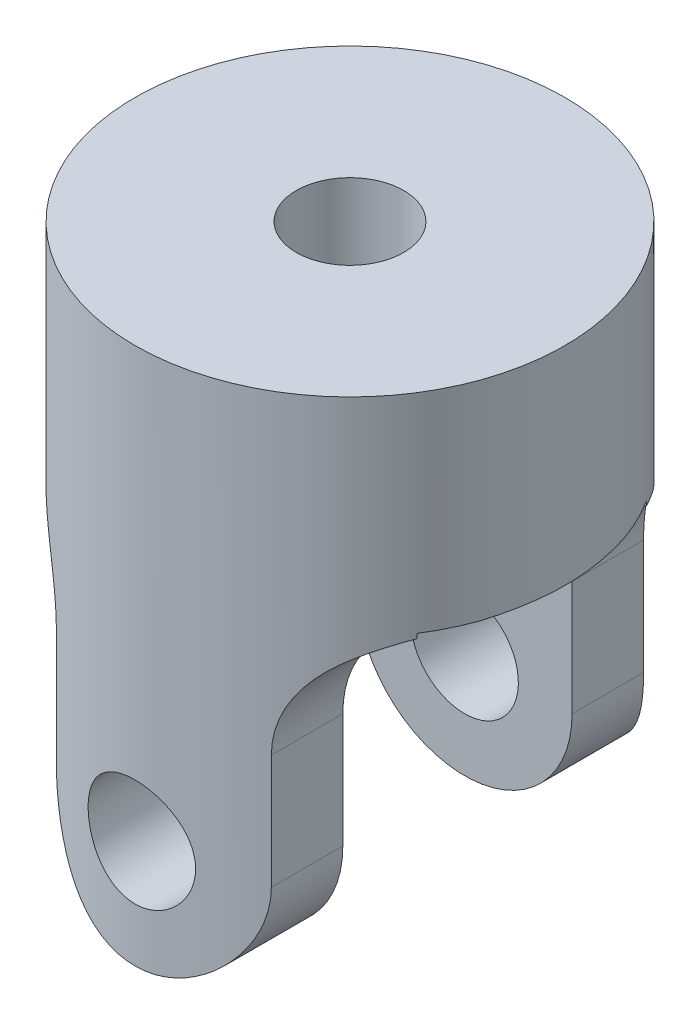
SolidWorks part; units mm, degrees
ref_plane "Front" through (0, 0, 0) normal (0, 0, 1) x (1, 0, 0)
ref_plane "Top" through (0, 0, 0) normal (0, 1, 0) x (-1, 0, 0)
ref_plane "Right" through (0, 0, 0) normal (1, 0, 0) x (0, 0, -1)
sketch "Sketch1" plane through (0, 0, 0) normal (0, 1, 0) x (-1, 0, 0)
  circle A0 centre (0, 0) radius 19.05
  dimension "D1" = 38.1
extrude "Base-Extrude" add sketch "Sketch1" along normal blind 47.625
sketch "Sketch2" plane through (0, 0, 0) normal (0, 0, 1) x (1, 0, 0)
  line L0 (0, 0) -> (0, 23.7435) construction
  line L1 (9.525, 9.525) -> (9.525, 19.685)
  line L2 (-9.525, 9.525) -> (-9.525, 19.685)
  line L3 (19.05, 29.21) -> (19.05, 0)
  line L4 (-19.05, 47.625) -> (-19.05, 0) construction
  line L5 (-19.05, 0) -> (-19.05, 29.21)
  line L6 (19.05, 0) -> (-19.05, 0) construction
  arc A0 (-9.525, 9.525) -> (9.525, 9.525) centre (0, 9.525) ccw
  arc A1 (9.525, 19.685) -> (19.05, 29.21) centre (19.05, 19.685) cw
  arc A2 (-9.525, 19.685) -> (-19.05, 29.21) centre (-19.05, 19.685) ccw
  dimension "D3" = 9.525
  dimension "D2" = 19.05
  dimension "D4" = 29.21
extrude "Cut-Extrude1" cut sketch "Sketch2" against normal through all and the other way through all flip side to cut
sketch "Sketch8" plane through (0, 0, 0) normal (1, 0, 0) x (0, 0, -1)
  line L0 (-19.05, 0) -> (19.05, 0) construction
  line L1 (-10.16, 0) -> (-10.16, 29.1452)
  line L2 (10.16, 29.1452) -> (-10.16, 29.1452)
  line L3 (10.16, 29.1452) -> (10.16, 0)
  line L4 (0, 0) -> (0, 14.3858) construction
  point P4 (0, 0)
  dimension "D1" = 29.1452
  dimension "D2" = 20.32
extrude "Cut-Extrude5" cut sketch "Sketch8" against normal through all and the other way through all flip side to cut
sketch "Sketch11" plane through (0, 0, 0) normal (0, 0, 1) x (1, 0, 0)
  circle A0 centre (0, 9.525) radius 4.7625
  dimension "D1" = 9.525
extrude "Cut-Extrude6" cut sketch "Sketch11" against normal through all and the other way through all
sketch "Sketch12" plane through (0, 47.625, 0) normal (0, 1, 0) x (-1, 0, 0)
  circle A0 centre (0, 0) radius 4.7625
  dimension "D1" = 9.525
extrude "Cut-Extrude7" cut sketch "Sketch12" against normal through all
ref_axis "Axis1" through (0, 92.3256, -0.0001) along (0, -1, 0)
scale "Scale1" scale about centroid uniform scaling yes scale factor 0.65
